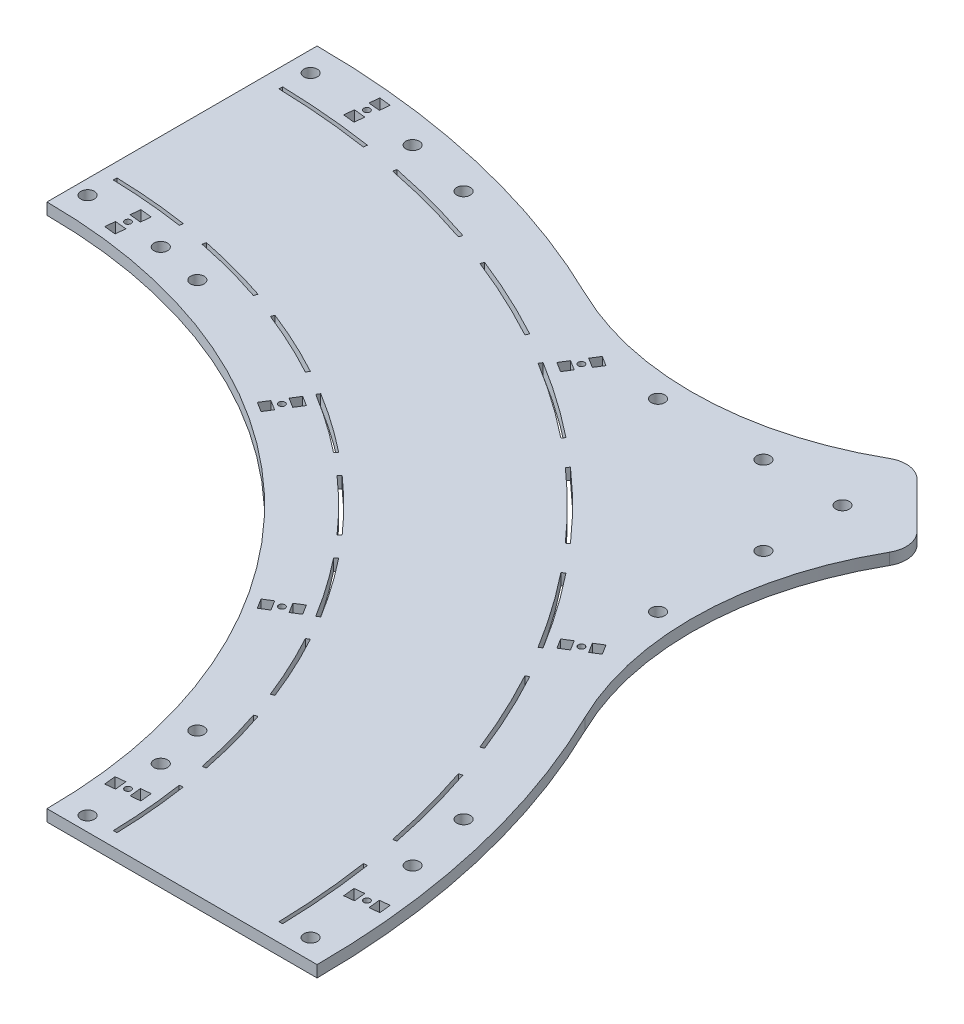
SolidWorks part; units mm, degrees
material "Custom Plastic"
ref_plane "Front Plane" through (0, 0, 0) normal (0, 0, 1) x (1, 0, 0)
ref_plane "Top Plane" through (0, 0, 0) normal (0, 1, 0) x (1, 0, 0)
ref_plane "Right Plane" through (0, 0, 0) normal (1, 0, 0) x (0, 0, -1)
sketch "Sketch1" plane through (0, 0, 0) normal (0, 1, 0) x (1, 0, 0)
  line L0 (280.2099, 0) -> (318.3099, 0)
  line L1 (318.3099, 0) -> (356.4099, 0)
  circle A0 centre (0, 0) radius 318.3099
  circle A1 centre (0, 0) radius 280.2099
  circle A2 centre (0, 0) radius 356.4099
  dimension "D1" = 636.6198
  dimension "D2" = 76.2
sketch "Sketch2" plane through (0, 0, 0) normal (0, 1, 0) x (1, 0, 0)
  line L0 (356.4099, 0) -> (383.3974, 0) construction
  line L1 (280.2099, 0) -> (253.2224, 0) construction
  line L2 (0, 0) -> (0, 470.2302) construction
  line L3 (0, 383.3974) -> (0, 253.2224)
  line L4 (383.3974, 0) -> (253.2224, 0)
  arc A0 (253.2224, 0) -> (0, 253.2224) centre (0, 0) ccw
  arc A1 (383.3974, 0) -> (0, 383.3974) centre (0, 0) ccw
  circle A3 centre (0, 0) radius 253.2224 construction
  circle A4 centre (0, 0) radius 383.3974 construction
  dimension "D1" = 26.9875
  dimension "D2" = 90
extrude "Boss-Extrude1" add sketch "Sketch2" along normal blind 5.588
sketch "Sketch6" plane through (0, 0, 0) normal (0, 1, 0) x (1, 0, 0)
  line L1 (318.3099, -318.3099) -> (-318.3099, -318.3099)
  line L2 (318.3099, -318.3099) -> (318.3099, 318.3099)
  line L3 (318.3099, 318.3099) -> (-318.3099, 318.3099)
  line L4 (-318.3099, -318.3099) -> (-318.3099, 318.3099)
  line L5 (318.3099, -318.3099) -> (-318.3099, 318.3099) construction
  line L6 (318.3099, 318.3099) -> (-318.3099, -318.3099) construction
  circle A0 centre (0, 0) radius 318.3099 construction
  point P0 (0, 0)
sketch "Sketch7" plane through (0, 0, 0) normal (0, 1, 0) x (1, 0, 0)
  line L5 (203.1455, 239.0665) -> (239.0665, 203.1455)
  line L6 (203.1455, 239.0665) -> (318.3099, 354.2309)
  line L7 (239.0665, 203.1455) -> (354.2309, 318.3099)
  line L8 (318.3099, 354.2309) -> (354.2309, 318.3099)
  line L9 (203.1455, 239.0665) -> (354.2309, 318.3099) construction
  line L10 (239.0665, 203.1455) -> (318.3099, 354.2309) construction
  line L11 (318.3099, 318.3099) -> (-318.3099, -318.3099) construction
  point P1 (278.6882, 278.6882)
  dimension "D1" = 25.4
  dimension "D2" = 25.4
extrude "Boss-Extrude2" add sketch "Sketch7" along normal up to surface (5.588 mm away) up to face at (192.117, 5.588, -192.117)
sketch "Sketch3" plane through (0, 0, 0) normal (0, 1, 0) x (1, 0, 0)
  line L0 (0, 0) -> (394.3921, 9.6387) construction
  line L1 (318.3099, 0) -> (356.4099, 0) construction
  line L2 (277.0593, 41.9013) -> (275.329, 41.6396)
  line L3 (0, 0) -> (390.0742, 58.9932) construction
  line L7 (354.1329, 53.5576) -> (352.4025, 53.2959)
  line L8 (358.053, 8.7506) -> (356.3035, 8.7079)
  line L10 (280.1262, 6.8461) -> (278.3768, 6.8034)
  arc A1 (356.3035, 8.7079) -> (352.4025, 53.2959) centre (0, 0) ccw
  circle A2 centre (0, 0) radius 356.4099 construction
  arc A4 (358.053, 8.7506) -> (354.1329, 53.5576) centre (0, 0) ccw
  arc A6 (278.3768, 6.8034) -> (275.329, 41.6396) centre (0, 0) ccw
  arc A7 (280.1262, 6.8461) -> (277.0593, 41.9013) centre (0, 0) ccw
  circle A8 centre (0, 0) radius 280.2099 construction
  dimension "D1" = 1.4
  dimension "D2" = 7.2
  dimension "D4" = 1.75
extrude "Cut-Extrude2" cut sketch "Sketch3" along normal through all
sketch "Rotation Axis" plane through (0, 0, 0) normal (0, 0, 1) x (1, 0, 0)
  line L0 (0, 0) -> (0, 52.4129)
pattern_circular "CirPattern1" count 36 over 360 about axis through (0, 0, 0) along (0, 1, 0) of "Cut-Extrude2"
sketch "Sketch8" plane through (0, 0, 0) normal (0, 1, 0) x (1, 0, 0)
  line L0 (0, 0) -> (216.6823, 22.7742) construction
  line L1 (253.2224, 0) -> (383.3974, 0) construction
  line L2 (256.8637, 24.1881) -> (261.6001, 24.6859)
  line L3 (256.8637, 24.1881) -> (256.2796, 29.7455)
  line L4 (261.6001, 24.6859) -> (261.016, 30.2433)
  line L5 (256.2796, 29.7455) -> (261.016, 30.2433)
  line L6 (256.8637, 24.1881) -> (261.016, 30.2433) construction
  line L7 (261.6001, 24.6859) -> (256.2796, 29.7455) construction
  line L8 (361.0647, 35.14) -> (365.8011, 35.6379)
  line L9 (361.0647, 35.14) -> (360.4806, 40.6974)
  line L10 (365.8011, 35.6379) -> (365.217, 41.1952)
  line L11 (360.4806, 40.6974) -> (365.217, 41.1952)
  line L12 (361.0647, 35.14) -> (365.217, 41.1952) construction
  line L13 (365.8011, 35.6379) -> (360.4806, 40.6974) construction
  line L14 (267.9153, 25.3496) -> (272.6517, 25.8475)
  line L15 (267.9153, 25.3496) -> (267.3312, 30.907)
  line L16 (272.6517, 25.8475) -> (272.0676, 31.4048)
  line L17 (267.3312, 30.907) -> (272.0676, 31.4048)
  line L18 (267.9153, 25.3496) -> (272.0676, 31.4048) construction
  line L19 (272.6517, 25.8475) -> (267.3312, 30.907) construction
  line L20 (372.1163, 36.3016) -> (376.8527, 36.7994)
  line L21 (372.1163, 36.3016) -> (371.5322, 41.859)
  line L22 (376.8527, 36.7994) -> (376.2686, 42.3568)
  line L23 (371.5322, 41.859) -> (376.2686, 42.3568)
  line L24 (372.1163, 36.3016) -> (376.2686, 42.3568) construction
  line L25 (376.8527, 36.7994) -> (371.5322, 41.859) construction
  line L26 (261.308, 27.4646) -> (267.6232, 28.1283) construction
  line L27 (365.5091, 38.4166) -> (371.8243, 39.0803) construction
  circle A0 centre (264.4656, 27.7965) radius 1.524
  circle A1 centre (368.6667, 38.7484) radius 1.524
  arc A2 (383.3974, 0) -> (288.4678, 252.5468) centre (0, 0) ccw construction
  arc A3 (253.2224, 0) -> (0, 253.2224) centre (0, 0) ccw construction
  point P5 (269.9914, 28.3772)
  point P6 (258.9398, 27.2157)
  point P7 (363.1409, 38.1676)
  point P13 (374.1925, 39.3292)
  point P29 (251.8352, 26.4689)
  point P30 (381.2971, 40.0759)
  dimension "D7" = 3.048
  dimension "D1" = 6
  dimension "D2" = 4.7625
  dimension "D3" = 5.588
  dimension "D4" = 6.35
  dimension "D5" = 4.7625
  dimension "D6" = 4.7625
extrude "Cut-Extrude3" cut sketch "Sketch8" along normal through all
pattern_circular "CirPattern3" count 4 every 26 about axis through (0, 0, 0) along (0, 1, 0) of "Cut-Extrude3"
sketch "Sketch9" plane through (0, 0, 0) normal (0, 1, 0) x (1, 0, 0)
  line L0 (0, 0) -> (448.7512, 120.2425) construction
  line L1 (0, 0) -> (532.0627, 93.817) construction
  line L2 (0, 0) -> (519.2379, 13.5967) construction
  line L3 (253.2224, 0) -> (383.3974, 0) construction
  line L4 (253.2224, 0) -> (383.3974, 0) construction
  circle A0 centre (256.8613, 68.8258) radius 3.2639
  circle A1 centre (261.8824, 46.1769) radius 3.2639
  circle A2 centre (0, 0) radius 265.9224 construction
  arc A3 (253.2224, 0) -> (0, 253.2224) centre (0, 0) ccw construction
  circle A4 centre (265.8313, 6.961) radius 3.2639
  circle A5 centre (365.0657, 64.3709) radius 3.2639
  circle A6 centre (358.0662, 95.9435) radius 3.2639
  circle A7 centre (0, 0) radius 370.6974 construction
  arc A8 (383.3974, 0) -> (288.4678, 252.5468) centre (0, 0) ccw construction
  circle A9 centre (370.5704, 9.7037) radius 3.2639
  point P29 (0, 0)
  point P30 (0, 0)
  dimension "D1" = 12.7
  dimension "D2" = 6.5278
  dimension "D4" = 15
  dimension "D5" = 12.7
  dimension "D3" = 10
  dimension "D6" = 1.5
extrude "Cut-Extrude4" cut sketch "Sketch9" along normal up to surface (5.588 mm away) up to face at (199.3841, 5.588, -319.0812)
ref_plane "Plane1" through (0, 0, 0) normal (-0.7071, 0, -0.7071) x (-0.7071, 0, 0.7071)
mirror "Mirror1" about plane through (0, 0, 0) normal (-0.7071, 0, -0.7071) of "Cut-Extrude4"
fillet "Fillet1" radius 152.4 2 edges at (288.4678, 2.794, -252.5468) (252.5468, 2.794, -288.4678)
sketch "Sketch10" plane through (0, 0, 0) normal (0, 1, 0) x (1, 0, 0)
  line L0 (318.3099, -318.3099) -> (318.3099, 318.3099) construction
  line L1 (318.3099, 318.3099) -> (-318.3099, 318.3099) construction
  line L2 (229.4099, 318.3099) -> (318.3099, 318.3099) construction
  line L3 (318.3099, 318.3099) -> (318.3099, 229.4099) construction
  circle A0 centre (318.3099, 229.4099) radius 3.2639
  circle A1 centre (229.4099, 318.3099) radius 3.2639
  circle A2 centre (318.3099, 318.3099) radius 3.2639
  circle A3 centre (318.3099, 280.2099) radius 3.2639
  circle A4 centre (280.2099, 318.3099) radius 3.2639
  dimension "D1" = 6.5278
  dimension "D2" = 88.9
  dimension "D3" = 50.8
  dimension "D4" = 50.8
extrude "Cut-Extrude5" cut sketch "Sketch10" along normal up to surface (5.588 mm away) up to face at (6.961, 5.588, -262.5674)
fillet "Fillet2" radius 12.7 2 edges at (354.2309, 2.794, -318.3099) (318.3099, 2.794, -354.2309)
equation "\"TrackDiameter\"= \"TrackLength\" / pi"
equation "\"D1@Sketch1\"=\"TrackDiameter\""
equation "\"TrackLength\"= 2000"
equation "\"CorridorWidth\"=76.2"
equation "\"D2@Sketch1\"=\"CorridorWidth\""
